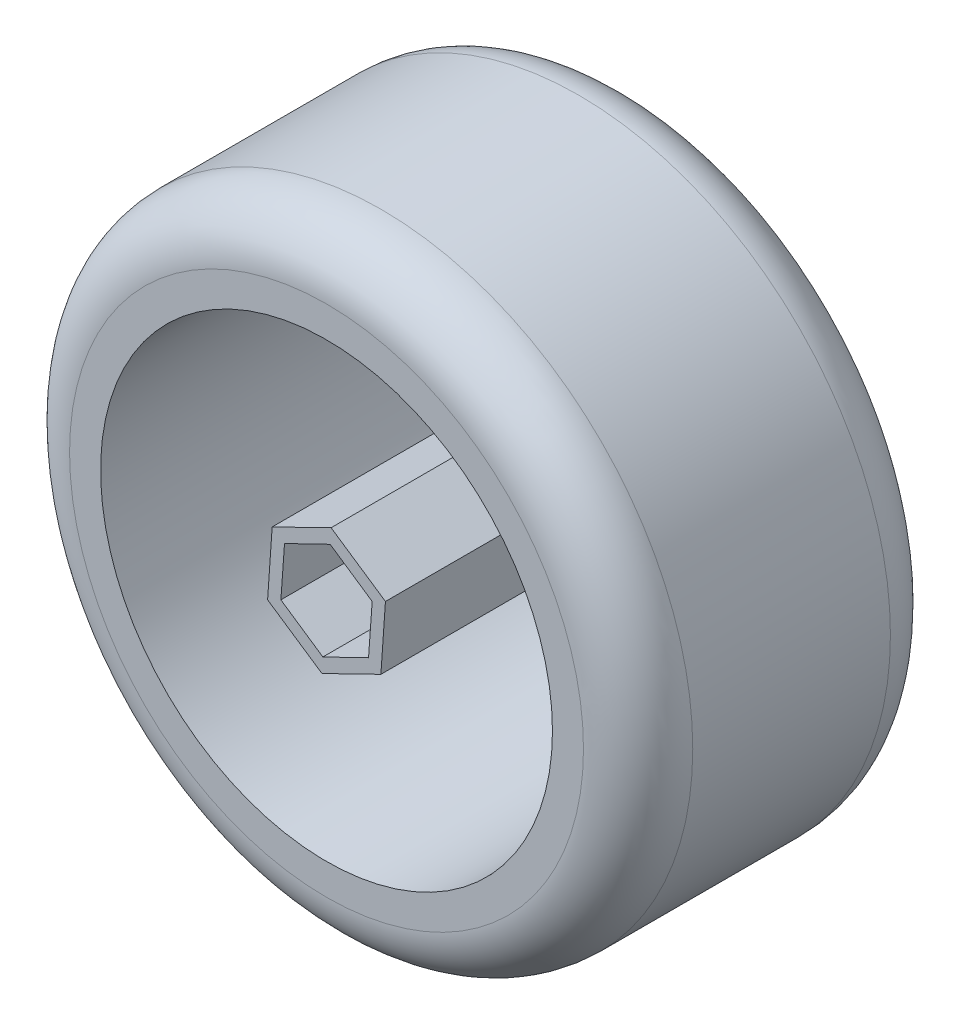
SolidWorks part; units mm, degrees
ref_plane "Front Plane" through (0, 0, 0) normal (0, 0, 1) x (1, 0, 0)
ref_plane "Top Plane" through (0, 0, 0) normal (0, 1, 0) x (1, 0, 0)
ref_plane "Right Plane" through (0, 0, 0) normal (1, 0, 0) x (0, 0, -1)
sketch "Sketch1" plane through (0, 0, 0) normal (0, 0, 1) x (1, 0, 0)
  circle A16 centre (0, 0) radius 42.545
  point P69 (0, 0)
  dimension "D1" = 85.09
extrude "Boss-Extrude1" add sketch "Sketch1" along normal blind 41.91
sketch "Sketch2" plane through (0, 0, 41.91) normal (0, 0, 1) x (1, 0, 0)
  line L1 (6.2338, 3.0232) -> (0.4987, 6.9102)
  line L2 (0.4987, 6.9102) -> (-5.7351, 3.887)
  line L3 (-5.7351, 3.887) -> (-6.2338, -3.0232)
  line L4 (-6.2338, -3.0232) -> (-0.4987, -6.9102)
  line L5 (-0.4987, -6.9102) -> (5.7351, -3.887)
  line L6 (5.7351, -3.887) -> (6.2338, 3.0232)
  circle A1 centre (0, 0) radius 6 construction
  dimension "D2" = 12
extrude "Cut-Extrude1" cut sketch "Sketch2" against normal through all
fillet "Fillet1" radius 7.46 2 edges at (42.545, 0, 0) (42.545, 0, 41.91)
sketch "Sketch3" plane through (0, 0, 41.91) normal (0, 0, 1) x (1, 0, 0)
  line L8 (0.6224, 8.9299) -> (-7.4223, 5.004)
  line L9 (-7.4223, 5.004) -> (-8.0447, -3.9259)
  line L10 (-8.0447, -3.9259) -> (-0.6224, -8.9299)
  line L11 (-0.6224, -8.9299) -> (7.4223, -5.004)
  line L12 (7.4223, -5.004) -> (8.0447, 3.9259)
  line L13 (8.0447, 3.9259) -> (0.6224, 8.9299)
  circle A0 centre (0, 0) radius 30.8492
  circle A1 centre (0, 0) radius 7.7522 construction
extrude "Cut-Extrude2" cut sketch "Sketch3" against normal through all
